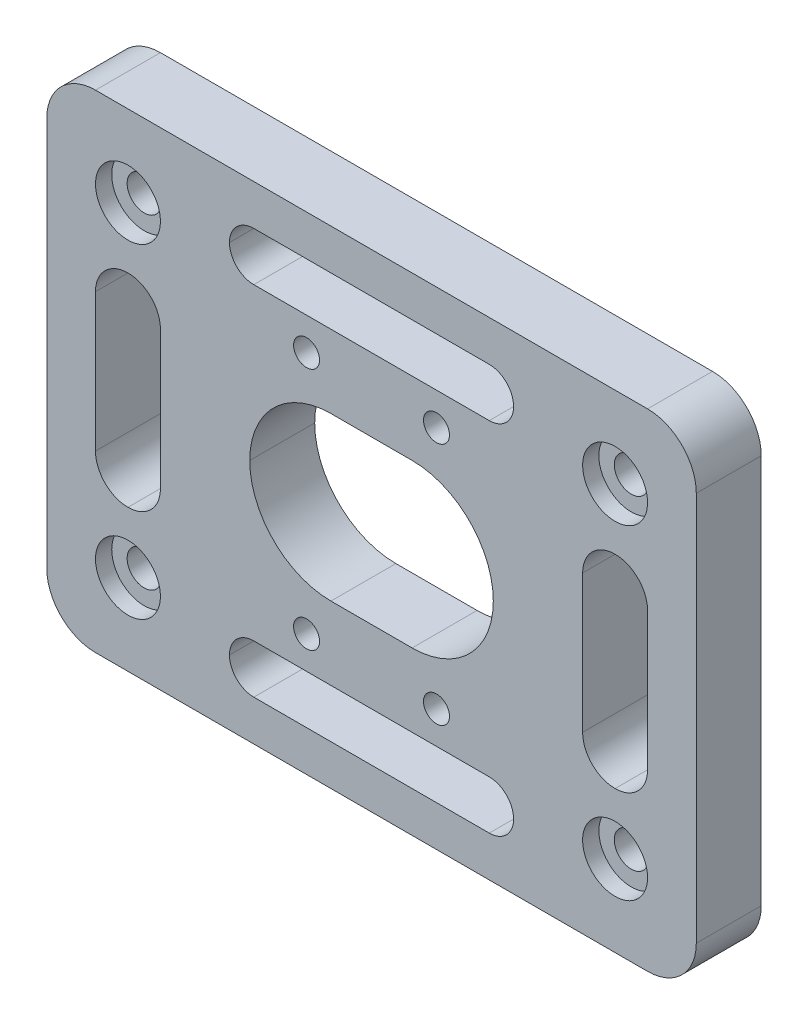
SolidWorks part; units mm, degrees
ref_plane "前视基准面" through (0, 0, 0) normal (0, 0, 1) x (1, 0, 0)
ref_plane "上视基准面" through (0, 0, 0) normal (0, 1, 0) x (1, 0, 0)
ref_plane "右视基准面" through (0, 0, 0) normal (1, 0, 0) x (0, 0, -1)
sketch "草图1" plane through (0, 0, 0) normal (0, 0, 1) x (1, 0, 0)
  line L0 (-10.9792, -3.2646) -> (49989.0208, -3.2646) construction
  line L1 (-50.9792, 26.7354) -> (29.0208, 26.7354)
  line L2 (-50.9792, 26.7354) -> (-50.9792, -33.2646)
  line L3 (-50.9792, -33.2646) -> (29.0208, -33.2646)
  line L4 (29.0208, 26.7354) -> (29.0208, -33.2646)
  line L5 (-50.9792, 26.7354) -> (29.0208, -33.2646) construction
  line L6 (-50.9792, -33.2646) -> (29.0208, 26.7354) construction
  line L7 (-10.9792, -3.2646) -> (-10.9792, 49996.7354) construction
  line L8 (-40.9792, 16.7354) -> (19.0208, 16.7354) construction
  line L9 (-29.9792, 22.7354) -> (8.0208, 22.7354) construction
  line L10 (-29.9792, 22.7354) -> (-29.9792, -29.2646) construction
  line L11 (-29.9792, -29.2646) -> (8.0208, -29.2646) construction
  line L12 (8.0208, 22.7354) -> (8.0208, -29.2646) construction
  line L13 (-29.9792, 22.7354) -> (8.0208, -29.2646) construction
  line L14 (-29.9792, -29.2646) -> (8.0208, 22.7354) construction
  line L15 (-18.9792, 11.7354) -> (-2.9792, 11.7354) construction
  line L16 (-18.9792, 11.7354) -> (-18.9792, -18.2646) construction
  line L17 (-18.9792, -18.2646) -> (-2.9792, -18.2646) construction
  line L18 (-2.9792, 11.7354) -> (-2.9792, -18.2646) construction
  line L19 (-18.9792, 11.7354) -> (-2.9792, -18.2646) construction
  line L20 (-18.9792, -18.2646) -> (-2.9792, 11.7354) construction
  line L21 (19.0208, 16.7354) -> (19.0208, -23.2646) construction
  line L22 (19.0208, -23.2646) -> (-40.9792, -23.2646) construction
  line L23 (-40.9792, -23.2646) -> (-40.9792, 16.7354) construction
  line L25 (-28.4792, 21.7354) -> (6.5208, 21.7354)
  line L26 (-28.4792, 21.7354) -> (-28.4792, 15.7354)
  line L27 (-28.4792, 15.7354) -> (6.5208, 15.7354)
  line L28 (6.5208, 21.7354) -> (6.5208, 15.7354)
  line L29 (-28.4792, 21.7354) -> (6.5208, 15.7354) construction
  line L30 (-28.4792, 15.7354) -> (6.5208, 21.7354) construction
  line L31 (-44.9792, 9.2354) -> (-36.9792, 9.2354)
  line L32 (-44.9792, 9.2354) -> (-44.9792, -15.7646)
  line L33 (-44.9792, -15.7646) -> (-36.9792, -15.7646)
  line L34 (-36.9792, 9.2354) -> (-36.9792, -15.7646)
  line L35 (-44.9792, 9.2354) -> (-36.9792, -15.7646) construction
  line L36 (-44.9792, -15.7646) -> (-36.9792, 9.2354) construction
  circle A0 centre (-40.9792, 16.7354) radius 2.1
  circle A1 centre (19.0208, 16.7354) radius 2.1
  circle A2 centre (19.0208, -23.2646) radius 2.1
  circle A3 centre (-40.9792, -23.2646) radius 2.1
  circle A4 centre (-18.9792, 11.7354) radius 3
  circle A5 centre (-2.9792, 11.7354) radius 3
  circle A6 centre (-2.9792, -18.2646) radius 3
  circle A7 centre (-18.9792, -18.2646) radius 3
  circle A8 centre (-18.9792, 11.7354) radius 1.6
  circle A9 centre (-2.9792, 11.7354) radius 1.6
  circle A10 centre (-2.9792, -18.2646) radius 1.6
  circle A11 centre (-18.9792, -18.2646) radius 1.6
  point P4 (-10.9792, -3.2646)
  point P9 (-40.9792, 16.7354)
  point P22 (-10.9792, -3.2646)
  point P27 (-10.9792, -3.2646)
  point P40 (-10.9792, 16.7354)
  point P41 (-10.9792, 16.7354)
  point P46 (-40.9792, -3.2646)
  point P47 (-40.9792, -3.2646)
  point P48 (0, 0)
  point P49 (0, 0)
  point P50 (-10.9792, 18.7354)
  point P53 (29.0208, 22.149)
  dimension "D5" = 4.2
  dimension "D10" = 6
  dimension "D11" = 3.2
  dimension "D1" = 80
  dimension "D2" = 60
  dimension "D3" = 10
  dimension "D4" = 10
  dimension "D6" = 38
  dimension "D7" = 52
  dimension "D8" = 16
  dimension "D9" = 30
  dimension "D12" = 35
  dimension "D13" = 6
  dimension "D14" = 8
  dimension "D15" = 25
  dimension "D16" = 22
  dimension "D17" = 40
extrude "凸台-拉伸2" add sketch "草图1" along normal blind 8 contours L4 L3 L2 L1 | A1 | A0 | A2 | A3 | A8 | A9 | A10 | A11
extrude "切除-拉伸2" cut sketch "草图1<3>" along normal blind 3.5 contours A5 | A4 | A6 | A7
sketch "草图1<3>" plane through (0, 0, 0) normal (0, 0, 1) x (1, 0, 0) same geometry as "草图1"
fillet "圆角1" radius 6 4 edges at (-50.9792, -33.2646, 4) (29.0208, -33.2646, 4) (29.0208, 26.7354, 4) (-50.9792, 26.7354, 4)
extrude "切除-拉伸3" cut sketch "草图1<4>" along normal through all contours L25 L28 L27 L26
sketch "草图1<4>" plane through (0, 0, 0) normal (0, 0, 1) x (1, 0, 0) same geometry as "草图1"
fillet "圆角2" radius 3 4 edges at (6.5208, 15.7354, 4) (6.5208, 21.7354, 4) (-28.4792, 15.7354, 4) (-28.4792, 21.7354, 4)
ref_plane "基准面4" through (0, -3.2646, 0) normal (0, 1, 0) x (1, 0, 0)
mirror "镜向1" about plane through (0, -3.2646, 0) normal (0, 1, 0) of "圆角2", "切除-拉伸3"
ref_plane "基准面5" through (-10.9792, 0, 0) normal (-1, 0, 0) x (0, 0, 1)
extrude "切除-拉伸4" cut sketch "草图1<5>" along normal through all contours L32 L33 L34 L31
sketch "草图1<5>" plane through (0, 0, 0) normal (0, 0, 1) x (1, 0, 0) same geometry as "草图1"
fillet "圆角3" radius 4 4 edges at (-36.9792, -15.7646, 4) (-44.9792, -15.7646, 4) (-36.9792, 9.2354, 4) (-44.9792, 9.2354, 4)
mirror "镜向2" about plane through (-10.9792, 0, 0) normal (-1, 0, 0) of "切除-拉伸4", "圆角3"
sketch "草图2" plane through (0, 0, 8) normal (0, 0, 1) x (1, 0, 0)
  line L0 (-10.9792, 15.5614) -> (-10.9792, -15.5614) construction
  line L1 (10.4174, -3.2646) -> (-10.4174, -3.2646) construction
  circle A0 centre (-40.9792, 16.7354) radius 4
  circle A1 centre (19.0208, 16.7354) radius 4
  circle A2 centre (19.0208, -23.2646) radius 4
  circle A3 centre (-40.9792, -23.2646) radius 4
  point P0 (-40.9792, 16.7354)
  dimension "D1" = 8
extrude "切除-拉伸5" cut sketch "草图2" against normal blind 2
sketch "草图3" plane through (0, 0, 8) normal (0, 0, 1) x (1, 0, 0)
  line L0 (-970.9792, -3.2646) -> (49029.0208, -3.2646) construction
  line L1 (29.0208, 20.7354) -> (29.0208, -27.2646) construction
  line L2 (-10.9792, -1033.2646) -> (-10.9792, 48966.7354) construction
  line L3 (-44.9792, -33.2646) -> (23.0208, -33.2646) construction
  line L5 (-25.9792, 6.7354) -> (4.0208, 6.7354)
  line L6 (-25.9792, 6.7354) -> (-25.9792, -13.2646)
  line L7 (-25.9792, -13.2646) -> (4.0208, -13.2646)
  line L8 (4.0208, 6.7354) -> (4.0208, -13.2646)
  point P5 (29.0208, -3.2646)
  point P10 (-10.9792, -33.2646)
  dimension "D1" = 15
  dimension "D2" = 10
extrude "切除-拉伸6" cut sketch "草图3" against normal blind 10
fillet "圆角4" radius 10 4 edges at (4.0208, -13.2646, 4) (-25.9792, -13.2646, 4) (4.0208, 6.7354, 4) (-25.9792, 6.7354, 4)
